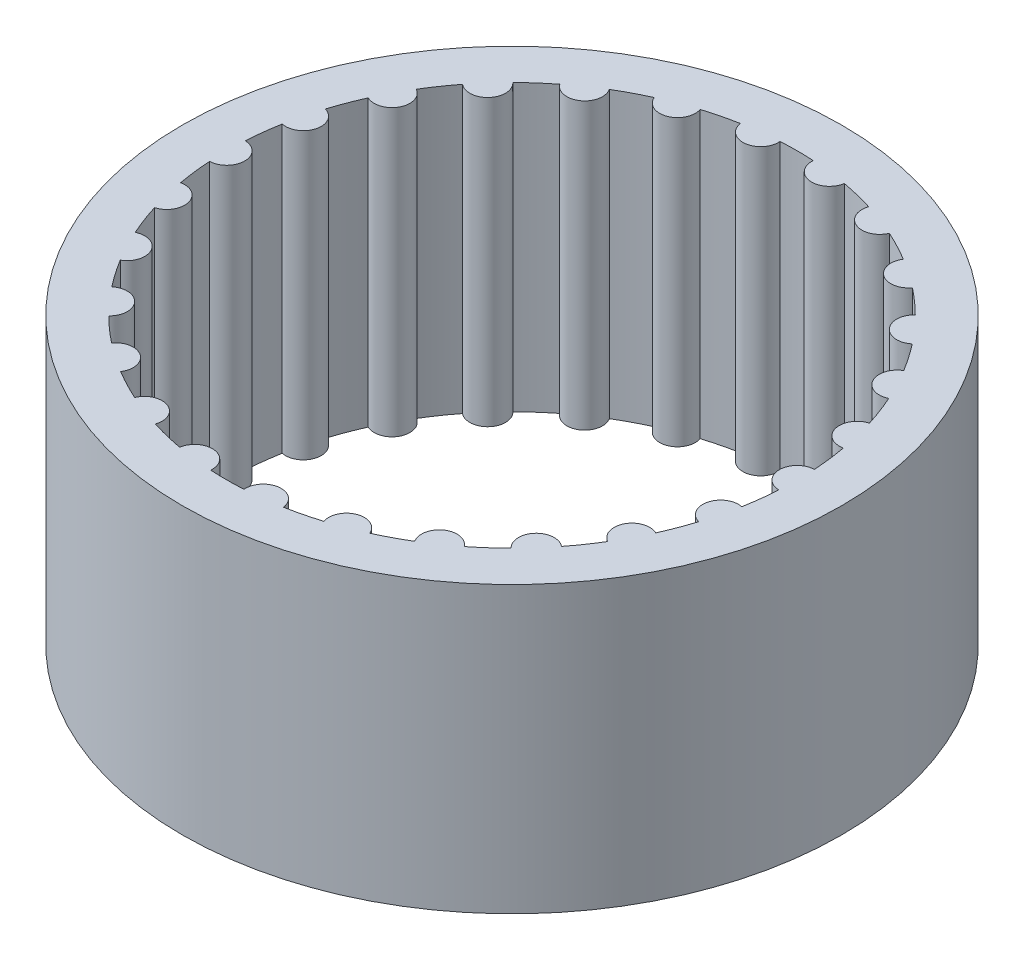
SolidWorks part; units mm, degrees
ref_plane "Front Plane" through (0, 0, 0) normal (0, 0, 1) x (1, 0, 0)
ref_plane "Top Plane" through (0, 0, 0) normal (0, 1, 0) x (1, 0, 0)
ref_plane "Right Plane" through (0, 0, 0) normal (1, 0, 0) x (0, 0, -1)
sketch "Sketch1" plane through (0, 0, 0) normal (0, 1, 0) x (1, 0, 0)
  circle A0 centre (15.5, 0) radius 1
  circle A1 centre (15.0351, -3.8291) radius 1
  circle A2 centre (13.6673, -7.4356) radius 1
  circle A3 centre (11.4762, -10.61) radius 1
  circle A4 centre (8.589, -13.1677) radius 1
  circle A5 centre (5.1737, -14.9603) radius 1
  circle A6 centre (1.4286, -15.8833) radius 1
  circle A7 centre (-2.4286, -15.8833) radius 1
  circle A8 centre (-6.1737, -14.9603) radius 1
  circle A9 centre (-9.589, -13.1677) radius 1
  circle A10 centre (-12.4762, -10.61) radius 1
  circle A11 centre (-14.6673, -7.4356) radius 1
  circle A12 centre (-16.0351, -3.8291) radius 1
  circle A13 centre (-16.5, 0) radius 1
  circle A14 centre (-16.0351, 3.8291) radius 1
  circle A15 centre (-14.6673, 7.4356) radius 1
  circle A16 centre (-12.4762, 10.61) radius 1
  circle A17 centre (-9.589, 13.1677) radius 1
  circle A18 centre (-6.1737, 14.9603) radius 1
  circle A19 centre (-2.4286, 15.8833) radius 1
  circle A20 centre (1.4286, 15.8833) radius 1
  circle A21 centre (5.1737, 14.9603) radius 1
  circle A22 centre (8.589, 13.1677) radius 1
  circle A23 centre (11.4762, 10.61) radius 1
  circle A24 centre (13.6673, 7.4356) radius 1
  circle A25 centre (15.0351, 3.8291) radius 1
  spline S0 degree 4 number of poles 315 (14.4, 0) -> (-15.4, 0) construction
sketch "Sketch2" plane through (0, 0, 0) normal (0, 1, 0) x (1, 0, 0)
  circle A0 centre (15.5, 0) radius 1
  circle A1 centre (15.0351, -3.8291) radius 1
  circle A2 centre (13.6673, -7.4356) radius 1
  circle A3 centre (11.4762, -10.61) radius 1
  circle A4 centre (8.589, -13.1677) radius 1
  circle A5 centre (5.1737, -14.9603) radius 1
  circle A6 centre (1.4286, -15.8833) radius 1
  circle A7 centre (-2.4286, -15.8833) radius 1
  circle A8 centre (-6.1737, -14.9603) radius 1
  circle A9 centre (-9.589, -13.1677) radius 1
  circle A10 centre (-12.4762, -10.61) radius 1
  circle A11 centre (-14.6673, -7.4356) radius 1
  circle A12 centre (-16.0351, -3.8291) radius 1
  circle A13 centre (-16.5, 0) radius 1
  circle A14 centre (-16.0351, 3.8291) radius 1
  circle A15 centre (-14.6673, 7.4356) radius 1
  circle A16 centre (-12.4762, 10.61) radius 1
  circle A17 centre (-9.589, 13.1677) radius 1
  circle A18 centre (-6.1737, 14.9603) radius 1
  circle A19 centre (-2.4286, 15.8833) radius 1
  circle A20 centre (1.4286, 15.8833) radius 1
  circle A21 centre (5.1737, 14.9603) radius 1
  circle A22 centre (8.589, 13.1677) radius 1
  circle A23 centre (11.4762, 10.61) radius 1
  circle A24 centre (13.6673, 7.4356) radius 1
  circle A25 centre (15.0351, 3.8291) radius 1
extrude "Boss-Extrude1" add sketch "Sketch2" along normal blind 8 and the other way blind 8
sketch "Sketch4" plane through (0, 0, 0) normal (0, 1, 0) x (1, 0, 0)
  line L0 (-15.4, 0) -> (14.4, 0) construction
  line L1 (0, 0) -> (0, 14.9128) construction
  line L2 (0, 0) -> (0, -14.9128) construction
  line L3 (0, 0) -> (-0.5, 0) construction
  line L4 (-0.5, 0) -> (-0.5, 15.3103) construction
  line L5 (-0.5, 0) -> (-0.5, -15.3103) construction
  line L6 (14.4, 0) -> (15.5, 0) construction
  line L7 (0, 0) -> (10, 0) construction
  line L8 (7.9, 0) -> (9.5, 0)
  line L9 (-0.5, 0) -> (9.5, 0) construction
  line L10 (-0.5, 15.3103) -> (-0.5, -15.3103) construction
  circle A0 centre (-0.5, 0) radius 16
  circle A1 centre (15.5, 0) radius 1
  circle A2 centre (15.0351, -3.8291) radius 1
  circle A3 centre (13.6673, -7.4356) radius 1
  circle A4 centre (11.4762, -10.61) radius 1
  circle A5 centre (8.589, -13.1677) radius 1
  circle A6 centre (5.1737, -14.9603) radius 1
  circle A7 centre (1.4286, -15.8833) radius 1
  circle A8 centre (-2.4286, -15.8833) radius 1
  circle A9 centre (-6.1737, -14.9603) radius 1
  circle A10 centre (-9.589, -13.1677) radius 1
  circle A11 centre (-12.4762, -10.61) radius 1
  circle A12 centre (-14.6673, -7.4356) radius 1
  circle A13 centre (-16.0351, -3.8291) radius 1
  circle A14 centre (-16.5, 0) radius 1
  circle A15 centre (-16.0351, 3.8291) radius 1
  circle A16 centre (-14.6673, 7.4356) radius 1
  circle A17 centre (-12.4762, 10.61) radius 1
  circle A18 centre (-9.589, 13.1677) radius 1
  circle A19 centre (-6.1737, 14.9603) radius 1
  circle A20 centre (-2.4286, 15.8833) radius 1
  circle A21 centre (1.4286, 15.8833) radius 1
  circle A22 centre (5.1737, 14.9603) radius 1
  circle A23 centre (8.589, 13.1677) radius 1
  circle A24 centre (11.4762, 10.61) radius 1
  circle A25 centre (13.6673, 7.4356) radius 1
  circle A26 centre (15.0351, 3.8291) radius 1
  circle A27 centre (0, 0) radius 10
  circle A28 centre (10, 0) radius 2.1
  circle A29 centre (5, -8.6603) radius 2.1
  circle A30 centre (-5, -8.6603) radius 2.1
  circle A31 centre (-10, 0) radius 2.1
  circle A32 centre (-5, 8.6603) radius 2.1
  circle A33 centre (5, 8.6603) radius 2.1
  circle A34 centre (-6, 8.6603) radius 2.1
  circle A35 centre (4, 8.6603) radius 2.1
  circle A36 centre (9, 0) radius 2.1
  circle A37 centre (4, -8.6603) radius 2.1
  circle A38 centre (-6, -8.6603) radius 2.1
  circle A39 centre (-1, 0) radius 10
  circle A40 centre (-11, 0) radius 2.1
  circle A41 centre (9.5, 0) radius 1.5
  circle A42 centre (4.5, -8.6603) radius 1.5
  circle A43 centre (-5.5, -8.6603) radius 1.5
  circle A44 centre (-10.5, 0) radius 1.5
  circle A45 centre (-5.5, 8.6603) radius 1.5
  circle A46 centre (4.5, 8.6603) radius 1.5
  circle A47 centre (-0.5, 0) radius 19.5
  circle A48 centre (0, 0) radius 5.55
  circle A49 centre (-0.5, 0) radius 5.55
  spline S0 degree 4 number of poles 369 (14.1521, 3.1658) -> (-14.9531, 3.4358) construction
  spline S1 degree 4 number of poles 315 (14.4, 0) -> (-15.4, 0)
  spline S2 degree 4 number of poles 315 (14.4, 0) -> (-15.4, 0)
  spline S3 degree 4 number of poles 315 (-15.4, 0) -> (14.4, 0)
  spline S4 degree 4 number of poles 315 (-15.4, 0) -> (14.4, 0)
  dimension "D1" = 32
  dimension "D2" = 2
  dimension "D4" = 20
  dimension "D5" = 4.2
  dimension "D8" = 6
  dimension "D7" = 10
  dimension "D9" = 10
  dimension "D3" = 26
  dimension "D6" = 6
sketch "Sketch5" plane through (0, 0, 0) normal (0, 1, 0) x (1, 0, 0)
  circle A0 centre (-0.5, 0) radius 16
  circle A1 centre (-0.5, 0) radius 18.5
extrude "Boss-Extrude3" add sketch "Sketch5" along normal blind 8 and the other way blind 8
